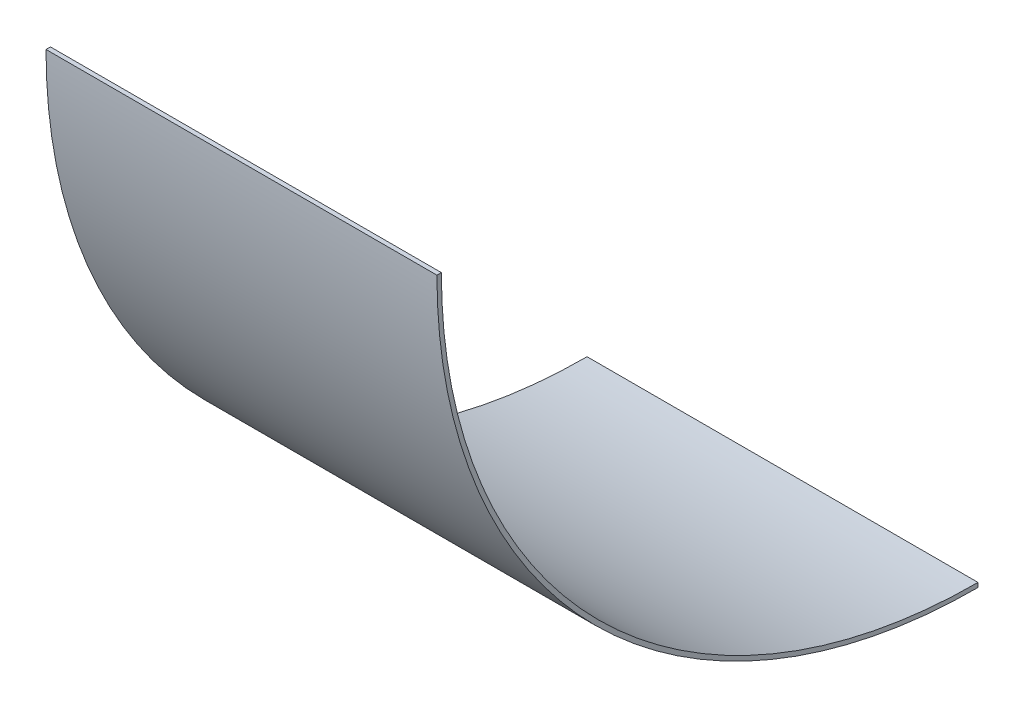
SolidWorks part; units mm, degrees
ref_plane "Front Plane" through (0, 0, 0) normal (0, 0, 1) x (1, 0, 0)
ref_plane "Top Plane" through (0, 0, 0) normal (0, 1, 0) x (1, 0, 0)
ref_plane "Right Plane" through (0, 0, 0) normal (1, 0, 0) x (0, 0, -1)
sketch "Sketch1" plane through (0, 0, 0) normal (1, 0, 0) x (0, 0, -1)
  arc A0 (-191.77, 0) -> (0, -191.77) centre (0, 0) ccw
  dimension "D1" = 383.54
extrude "Extrude-Thin1" add sketch "Sketch1" along normal blind 139.7 thin thin type one direction wall 1.5875
